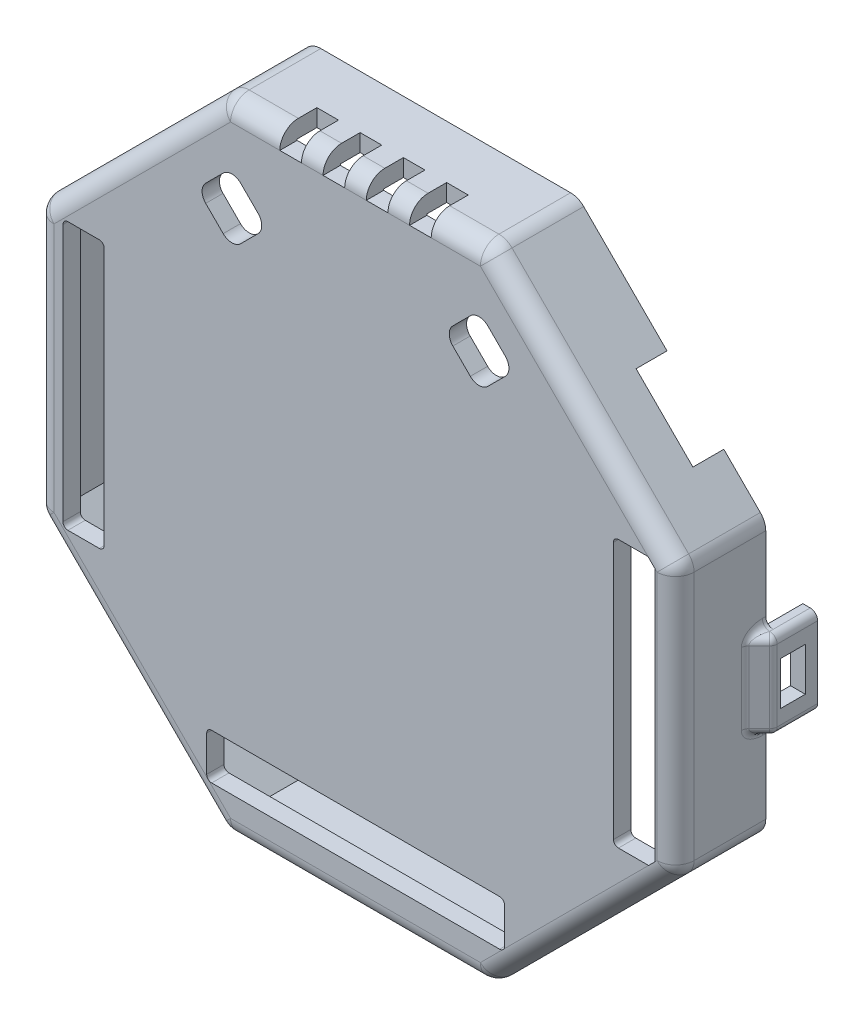
SolidWorks part; units mm, degrees
ref_plane "Front Plane" through (0, 0, 0) normal (0, 0, 1) x (1, 0, 0)
ref_plane "Top Plane" through (0, 0, 0) normal (0, 1, 0) x (1, 0, 0)
ref_plane "Right Plane" through (0, 0, 0) normal (1, 0, 0) x (0, 0, -1)
sketch "Sketch1" plane through (0, 0, 0) normal (0, 0, 1) x (1, 0, 0)
  line L0 (25.9, -10.1068) -> (25.9, 10.1068) construction
  line L1 (25.4607, 11.1675) -> (22.5059, 14.1222) construction
  line L2 (22.5059, 14.1222) -> (21.5159, 13.1323) construction
  line L3 (21.5159, 13.1323) -> (24.5, 10.1482) construction
  line L4 (24.5, 10.1482) -> (24.5, -10.1482) construction
  line L5 (24.5, -10.1482) -> (21.6927, -12.9555) construction
  line L6 (21.6927, -12.9555) -> (22.6827, -13.9455) construction
  line L7 (22.6827, -13.9455) -> (25.4607, -11.1675) construction
  line L8 (-16.1773, -20.4508) -> (-11.1675, -25.4607) construction
  line L9 (-10.1068, -25.9) -> (10.1068, -25.9) construction
  line L10 (11.1675, -25.4607) -> (15.6116, -21.0165) construction
  line L11 (15.6116, -21.0165) -> (14.6216, -20.0266) construction
  line L12 (14.6216, -20.0266) -> (10.1482, -24.5) construction
  line L13 (10.1482, -24.5) -> (-10.1482, -24.5) construction
  line L14 (-10.1482, -24.5) -> (-15.1873, -19.4609) construction
  line L15 (-15.1873, -19.4609) -> (-16.1773, -20.4508) construction
  line L16 (-22.117, 14.5112) -> (-25.4607, 11.1675) construction
  line L17 (-25.9, 10.1068) -> (-25.9, -10.1068) construction
  line L18 (-25.4607, -11.1675) -> (-22.1877, -14.4404) construction
  line L19 (-22.1877, -14.4404) -> (-21.1977, -13.4505) construction
  line L20 (-21.1977, -13.4505) -> (-24.5, -10.1482) construction
  line L21 (-24.5, -10.1482) -> (-24.5, 10.1482) construction
  line L22 (-24.5, 10.1482) -> (-21.127, 13.5212) construction
  line L23 (-21.127, 13.5212) -> (-22.117, 14.5112) construction
  line L24 (10.1068, 25.9) -> (-10.1068, 25.9) construction
  line L25 (-11.1675, 25.4607) -> (-17.5208, 19.1073) construction
  line L26 (-17.5208, 19.1073) -> (-16.5308, 18.1174) construction
  line L27 (-16.5308, 18.1174) -> (-10.1482, 24.5) construction
  line L28 (-10.1482, 24.5) -> (10.1482, 24.5) construction
  line L29 (10.1482, 24.5) -> (16.9197, 17.7285) construction
  line L30 (16.9197, 17.7285) -> (17.9097, 18.7184) construction
  line L31 (17.9097, 18.7184) -> (11.1675, 25.4607) construction
  line L32 (25.9, -10.1068) -> (25.9, 10.1068)
  line L33 (25.4607, 11.1675) -> (22.5059, 14.1222)
  line L34 (22.5059, 14.1222) -> (21.5159, 13.1323)
  line L35 (21.5159, 13.1323) -> (24.5, 10.1482)
  line L36 (24.5, 10.1482) -> (24.5, -10.1482)
  line L37 (24.5, -10.1482) -> (21.6927, -12.9555)
  line L38 (21.6927, -12.9555) -> (22.6827, -13.9455)
  line L39 (22.6827, -13.9455) -> (25.4607, -11.1675)
  line L40 (-16.1773, -20.4508) -> (-11.1675, -25.4607)
  line L41 (-10.1068, -25.9) -> (10.1068, -25.9)
  line L42 (11.1675, -25.4607) -> (15.6116, -21.0165)
  line L43 (15.6116, -21.0165) -> (14.6216, -20.0266)
  line L44 (14.6216, -20.0266) -> (10.1482, -24.5)
  line L45 (10.1482, -24.5) -> (-10.1482, -24.5)
  line L46 (-10.1482, -24.5) -> (-15.1873, -19.4609)
  line L47 (-15.1873, -19.4609) -> (-16.1773, -20.4508)
  line L48 (-22.117, 14.5112) -> (-25.4607, 11.1675)
  line L49 (-25.9, 10.1068) -> (-25.9, -10.1068)
  line L50 (-25.4607, -11.1675) -> (-22.1877, -14.4404)
  line L51 (-22.1877, -14.4404) -> (-21.1977, -13.4505)
  line L52 (-21.1977, -13.4505) -> (-24.5, -10.1482)
  line L53 (-24.5, -10.1482) -> (-24.5, 10.1482)
  line L54 (-24.5, 10.1482) -> (-21.127, 13.5212)
  line L55 (-21.127, 13.5212) -> (-22.117, 14.5112)
  line L56 (10.1068, 25.9) -> (-10.1068, 25.9)
  line L57 (-11.1675, 25.4607) -> (-17.5208, 19.1073)
  line L58 (-17.5208, 19.1073) -> (-16.5308, 18.1174)
  line L59 (-16.5308, 18.1174) -> (-10.1482, 24.5)
  line L60 (-10.1482, 24.5) -> (10.1482, 24.5)
  line L61 (10.1482, 24.5) -> (16.9197, 17.7285)
  line L62 (16.9197, 17.7285) -> (17.9097, 18.7184)
  line L63 (17.9097, 18.7184) -> (11.1675, 25.4607)
  line L66 (-17.5208, 19.1073) -> (-16.5308, 18.1174)
  line L67 (-21.127, 13.5212) -> (-22.117, 14.5112)
  arc A0 (25.9, 10.1068) -> (25.4607, 11.1675) centre (24.4, 10.1068) ccw construction
  arc A1 (25.4607, -11.1675) -> (25.9, -10.1068) centre (24.4, -10.1068) ccw construction
  arc A2 (-11.1675, -25.4607) -> (-10.1068, -25.9) centre (-10.1068, -24.4) ccw construction
  arc A3 (10.1068, -25.9) -> (11.1675, -25.4607) centre (10.1068, -24.4) ccw construction
  arc A4 (-25.4607, 11.1675) -> (-25.9, 10.1068) centre (-24.4, 10.1068) ccw construction
  arc A5 (-25.9, -10.1068) -> (-25.4607, -11.1675) centre (-24.4, -10.1068) ccw construction
  arc A6 (-10.1068, 25.9) -> (-11.1675, 25.4607) centre (-10.1068, 24.4) ccw construction
  arc A7 (11.1675, 25.4607) -> (10.1068, 25.9) centre (10.1068, 24.4) ccw construction
  arc A8 (25.9, 10.1068) -> (25.4607, 11.1675) centre (24.4, 10.1068) ccw
  arc A9 (25.4607, -11.1675) -> (25.9, -10.1068) centre (24.4, -10.1068) ccw
  arc A10 (-11.1675, -25.4607) -> (-10.1068, -25.9) centre (-10.1068, -24.4) ccw
  arc A11 (10.1068, -25.9) -> (11.1675, -25.4607) centre (10.1068, -24.4) ccw
  arc A12 (-25.4607, 11.1675) -> (-25.9, 10.1068) centre (-24.4, 10.1068) ccw
  arc A13 (-25.9, -10.1068) -> (-25.4607, -11.1675) centre (-24.4, -10.1068) ccw
  arc A14 (-10.1068, 25.9) -> (-11.1675, 25.4607) centre (-10.1068, 24.4) ccw
  arc A15 (11.1675, 25.4607) -> (10.1068, 25.9) centre (10.1068, 24.4) ccw
extrude "Boss-Extrude1" add sketch "Sketch1" along normal blind 5 contours L63 A15 L56 A14 L57 L58 L59 L60 L61 L62 | L49 A13 L50 L51 L52 L53 L54 L55 L48 A12 | L41 A11 L42 L43 L44 L45 L46 L47 L40 A10 | L39 A9 L32 A8 L33 L34 L35 L36 L37 L38 region at (24.747, 0.1144, 0) region at (-15.453, -20.1852, 0) region at (-24.631, 0.0454, 0) region at (10.5417, 25.4499, 0)
sketch "Sketch2" plane through (0, 0, 5) normal (0, 0, 1) x (1, 0, 0)
  line L0 (22.6827, -13.9455) -> (25.4607, -11.1675) construction
  line L1 (25.9, -10.1068) -> (25.9, 10.1068) construction
  line L2 (25.4607, 11.1675) -> (22.5059, 14.1222) construction
  line L3 (22.5059, 14.1222) -> (21.5159, 13.1323) construction
  line L4 (21.5159, 13.1323) -> (24.5, 10.1482) construction
  line L5 (24.5, 10.1482) -> (24.5, -10.1482) construction
  line L6 (24.5, -10.1482) -> (21.6927, -12.9555) construction
  line L7 (21.6927, -12.9555) -> (22.6827, -13.9455) construction
  line L8 (-10.1068, -25.9) -> (10.1068, -25.9) construction
  line L9 (11.1675, -25.4607) -> (15.6116, -21.0165) construction
  line L10 (15.6116, -21.0165) -> (14.6216, -20.0266) construction
  line L11 (14.6216, -20.0266) -> (10.1482, -24.5) construction
  line L12 (10.1482, -24.5) -> (-10.1482, -24.5) construction
  line L13 (-10.1482, -24.5) -> (-15.1873, -19.4609) construction
  line L14 (-15.1873, -19.4609) -> (-16.1773, -20.4508) construction
  line L15 (-16.1773, -20.4508) -> (-11.1675, -25.4607) construction
  line L16 (-25.9, 10.1068) -> (-25.9, -10.1068) construction
  line L17 (-25.4607, -11.1675) -> (-22.1877, -14.4404) construction
  line L18 (-22.1877, -14.4404) -> (-21.1977, -13.4505) construction
  line L19 (-21.1977, -13.4505) -> (-24.5, -10.1482) construction
  line L20 (-24.5, -10.1482) -> (-24.5, 10.1482) construction
  line L21 (-24.5, 10.1482) -> (-21.127, 13.5212) construction
  line L22 (-21.127, 13.5212) -> (-22.117, 14.5112) construction
  line L23 (-22.117, 14.5112) -> (-25.4607, 11.1675) construction
  line L24 (17.9097, 18.7184) -> (11.1675, 25.4607) construction
  line L25 (10.1068, 25.9) -> (-10.1068, 25.9) construction
  line L26 (-11.1675, 25.4607) -> (-17.5208, 19.1073) construction
  line L27 (-17.5208, 19.1073) -> (-16.5308, 18.1174) construction
  line L28 (-16.5308, 18.1174) -> (-10.1482, 24.5) construction
  line L29 (-10.1482, 24.5) -> (10.1482, 24.5) construction
  line L30 (10.1482, 24.5) -> (16.9197, 17.7285) construction
  line L31 (16.9197, 17.7285) -> (17.9097, 18.7184) construction
  line L32 (22.6827, -13.9455) -> (25.4607, -11.1675)
  line L33 (25.9, -10.1068) -> (25.9, 10.1068)
  line L34 (25.4607, 11.1675) -> (22.5059, 14.1222)
  line L35 (22.5059, 14.1222) -> (21.5159, 13.1323)
  line L36 (21.5159, 13.1323) -> (24.5, 10.1482)
  line L37 (24.5, 10.1482) -> (24.5, -10.1482)
  line L38 (24.5, -10.1482) -> (21.6927, -12.9555)
  line L39 (21.6927, -12.9555) -> (22.6827, -13.9455)
  line L40 (-10.1068, -25.9) -> (10.1068, -25.9)
  line L41 (11.1675, -25.4607) -> (15.6116, -21.0165)
  line L42 (15.6116, -21.0165) -> (14.6216, -20.0266)
  line L43 (14.6216, -20.0266) -> (10.1482, -24.5)
  line L44 (10.1482, -24.5) -> (-10.1482, -24.5)
  line L45 (-10.1482, -24.5) -> (-15.1873, -19.4609)
  line L46 (-15.1873, -19.4609) -> (-16.1773, -20.4508)
  line L47 (-16.1773, -20.4508) -> (-11.1675, -25.4607)
  line L48 (-25.9, 10.1068) -> (-25.9, -10.1068)
  line L49 (-25.4607, -11.1675) -> (-22.1877, -14.4404)
  line L50 (-22.1877, -14.4404) -> (-21.1977, -13.4505)
  line L51 (-21.1977, -13.4505) -> (-24.5, -10.1482)
  line L52 (-24.5, -10.1482) -> (-24.5, 10.1482)
  line L53 (-24.5, 10.1482) -> (-21.127, 13.5212)
  line L54 (-21.127, 13.5212) -> (-22.117, 14.5112)
  line L55 (-22.117, 14.5112) -> (-25.4607, 11.1675)
  line L56 (17.9097, 18.7184) -> (11.1675, 25.4607)
  line L57 (10.1068, 25.9) -> (-10.1068, 25.9)
  line L58 (-11.1675, 25.4607) -> (-17.5208, 19.1073)
  line L59 (-17.5208, 19.1073) -> (-16.5308, 18.1174)
  line L60 (-16.5308, 18.1174) -> (-10.1482, 24.5)
  line L61 (-10.1482, 24.5) -> (10.1482, 24.5)
  line L62 (10.1482, 24.5) -> (16.9197, 17.7285)
  line L63 (16.9197, 17.7285) -> (17.9097, 18.7184)
  line L64 (-22.117, 14.5112) -> (-17.5208, 19.1073)
  line L65 (-16.5308, 18.1174) -> (-21.127, 13.5212)
  line L66 (-21.1977, -13.4505) -> (-15.1873, -19.4609)
  line L67 (-16.1773, -20.4508) -> (-22.1877, -14.4404)
  line L68 (14.6216, -20.0266) -> (21.6927, -12.9555)
  line L69 (22.6827, -13.9455) -> (15.6116, -21.0165)
  line L70 (22.5059, 14.1222) -> (17.9097, 18.7184)
  line L71 (21.5159, 13.1323) -> (16.9197, 17.7285)
  arc A0 (25.4607, -11.1675) -> (25.9, -10.1068) centre (24.4, -10.1068) ccw construction
  arc A1 (25.9, 10.1068) -> (25.4607, 11.1675) centre (24.4, 10.1068) ccw construction
  arc A2 (10.1068, -25.9) -> (11.1675, -25.4607) centre (10.1068, -24.4) ccw construction
  arc A3 (-11.1675, -25.4607) -> (-10.1068, -25.9) centre (-10.1068, -24.4) ccw construction
  arc A4 (-25.9, -10.1068) -> (-25.4607, -11.1675) centre (-24.4, -10.1068) ccw construction
  arc A5 (-25.4607, 11.1675) -> (-25.9, 10.1068) centre (-24.4, 10.1068) ccw construction
  arc A6 (11.1675, 25.4607) -> (10.1068, 25.9) centre (10.1068, 24.4) ccw construction
  arc A7 (-10.1068, 25.9) -> (-11.1675, 25.4607) centre (-10.1068, 24.4) ccw construction
  arc A8 (25.4607, -11.1675) -> (25.9, -10.1068) centre (24.4, -10.1068) ccw
  arc A9 (25.9, 10.1068) -> (25.4607, 11.1675) centre (24.4, 10.1068) ccw
  arc A10 (10.1068, -25.9) -> (11.1675, -25.4607) centre (10.1068, -24.4) ccw
  arc A11 (-11.1675, -25.4607) -> (-10.1068, -25.9) centre (-10.1068, -24.4) ccw
  arc A12 (-25.9, -10.1068) -> (-25.4607, -11.1675) centre (-24.4, -10.1068) ccw
  arc A13 (-25.4607, 11.1675) -> (-25.9, 10.1068) centre (-24.4, 10.1068) ccw
  arc A14 (11.1675, 25.4607) -> (10.1068, 25.9) centre (10.1068, 24.4) ccw
  arc A15 (-10.1068, 25.9) -> (-11.1675, 25.4607) centre (-10.1068, 24.4) ccw
  line M21 (17.9097, 18.7184) -> (11.1675, 25.4607)
  arc M22 (11.1675, 25.4607) -> (10.1068, 25.9) centre (10.1068, 24.4) ccw
  line M23 (10.1068, 25.9) -> (-10.1068, 25.9)
  arc M24 (-10.1068, 25.9) -> (-11.1675, 25.4607) centre (-10.1068, 24.4) ccw
  line M25 (-11.1675, 25.4607) -> (-17.5208, 19.1073)
  line M26 (-17.5208, 19.1073) -> (-16.5308, 18.1174)
  line M27 (-16.5308, 18.1174) -> (-10.1482, 24.5)
  line M28 (-10.1482, 24.5) -> (10.1482, 24.5)
  line M29 (10.1482, 24.5) -> (16.9197, 17.7285)
  line M30 (16.9197, 17.7285) -> (17.9097, 18.7184)
extrude "Boss-Extrude2" add sketch "Sketch2" along normal blind 1.4 contours L36 L71 L65 L53 L52 L51 L66 L45 L44 L43 L68 L38 L37 M29 M28 M27 | L33 A9 L34 L35 L36 L37 L38 L39 L32 A8 | L69 L39 L68 L42 | L47 A11 L40 A10 L41 L42 L43 L44 L45 L46 | L67 L46 L66 L50 | L55 A13 L48 A12 L49 L50 L51 L52 L53 L54 | L65 L64 L54 M26 | M30 M21 M22 M23 M24 M25 M26 M27 M28 M29 | L71 L35 L70 M30 region at (24.747, 0.1144, 5) region at (18.6522, -16.986, 5) region at (0, 0, 5) region at (13.1602, -23.0093, 5) region at (19.7128, 15.9254, 5) region at (13.7911, 21.3714, 5) region at (-18.6875, -16.9507, 5) region at (-24.631, 0.0454, 5) region at (-19.3239, 16.3143, 5)
sketch "Sketch3" plane through (0, 0, 5) normal (0, 0, -1) x (-1, 0, 0)
  line L0 (-21.5159, 13.1323) -> (-16.9197, 17.7285)
  line L1 (-16.9197, 17.7285) -> (-17.9097, 18.7184)
  line L2 (-17.9097, 18.7184) -> (-22.5059, 14.1222)
  line L3 (-22.5059, 14.1222) -> (-21.5159, 13.1323)
  line L4 (21.127, 13.5212) -> (16.5308, 18.1174)
  line L5 (16.5308, 18.1174) -> (17.5208, 19.1073)
  line L6 (17.5208, 19.1073) -> (22.117, 14.5112)
  line L7 (22.117, 14.5112) -> (21.127, 13.5212)
extrude "Boss-Extrude3" add sketch "Sketch3" along normal blind 3.4 contours L7 L4 L5 L6 | L3 L0 L1 L2
sketch "Sketch4" plane through (0, 0, 5) normal (0, 0, -1) x (-1, 0, 0)
  line L0 (-15.6116, -21.0165) -> (-14.6216, -20.0266)
  line L1 (-14.6216, -20.0266) -> (-21.6927, -12.9555)
  line L2 (-21.6927, -12.9555) -> (-22.6827, -13.9455)
  line L3 (-22.6827, -13.9455) -> (-15.6116, -21.0165)
extrude "Boss-Extrude4" add sketch "Sketch4" along normal blind 3.4
sketch "Sketch5" plane through (0, 0, 5) normal (0, 0, -1) x (-1, 0, 0)
  line L0 (16.1773, -20.4508) -> (22.1877, -14.4404)
  line L1 (22.1877, -14.4404) -> (21.1977, -13.4505)
  line L2 (21.1977, -13.4505) -> (15.1873, -19.4609)
  line L3 (15.1873, -19.4609) -> (16.1773, -20.4508)
extrude "Boss-Extrude5" add sketch "Sketch5" along normal blind 1
fillet "Fillet1" radius 1.5 18 edges at (10.6808, -25.7858, 6.4) (0, -25.9, 6.4) (-10.6808, -25.7858, 6.4) (-18.3141, -18.3141, 6.4) (-25.7858, -10.6808, 6.4) (-25.9, 0, 6.4) (-25.7858, 10.6808, 6.4) (-18.3141, 18.3141, 6.4) (-10.6808, 25.7858, 6.4) (0, 25.9, 6.4) (10.6808, 25.7858, 6.4) (18.3141, 18.3141, 6.4) (25.7858, 10.6808, 6.4) (25.9, 0, 6.4) (25.7858, -10.6808, 6.4) (18.3141, -18.3141, 6.4) (15.1166, -20.5216, 1.6) (22.1877, -13.4505, 1.6)
sketch "Sketch6" plane through (0, 0, 6.4) normal (0, 0, 1) x (1, 0, 0)
  line L0 (-23.2729, -10.394) -> (-20.7329, -10.394) construction
  line L1 (-23.2729, 10.434) -> (-23.2729, -10.394) construction
  line L2 (-20.7329, -10.394) -> (-20.7329, 10.434) construction
  line L3 (-20.7329, 10.434) -> (-23.2729, 10.434) construction
  line L4 (21.2779, -10.389) -> (23.8179, -10.389) construction
  line L5 (23.8179, -10.389) -> (23.8179, 10.439) construction
  line L6 (21.2779, 10.439) -> (21.2779, -10.389) construction
  line L7 (23.8179, 10.439) -> (21.2779, 10.439) construction
  line L8 (-23.2729, -10.394) -> (-20.7329, -10.394)
  line L9 (-23.2729, 10.434) -> (-23.2729, -10.394)
  line L10 (-20.7329, -10.394) -> (-20.7329, 10.434)
  line L11 (-20.7329, 10.434) -> (-23.2729, 10.434)
  line L12 (21.2779, -10.389) -> (23.8179, -10.389)
  line L13 (23.8179, -10.389) -> (23.8179, 10.439)
  line L14 (21.2779, 10.439) -> (21.2779, -10.389)
  line L15 (23.8179, 10.439) -> (21.2779, 10.439)
  line L16 (-20.3329, -10.394) -> (-20.3329, 10.434)
  line L17 (-20.7329, 10.834) -> (-23.2729, 10.834)
  line L18 (-23.6729, 10.434) -> (-23.6729, -10.394)
  line L19 (-23.2729, -10.794) -> (-20.7329, -10.794)
  line L20 (21.2779, -10.789) -> (23.8179, -10.789)
  line L21 (24.2179, -10.389) -> (24.2179, 10.439)
  line L22 (23.8179, 10.839) -> (21.2779, 10.839)
  line L23 (20.8779, 10.439) -> (20.8779, -10.389)
  line L24 (24.2179, 10.839) -> (20.8779, 10.839) construction
  line L25 (20.8779, 10.839) -> (20.8779, -10.789) construction
  line L26 (24.2179, -10.789) -> (24.2179, 10.839) construction
  line L27 (20.8779, -10.789) -> (24.2179, -10.789) construction
  line L28 (-20.3329, -10.794) -> (-20.3329, 10.834) construction
  line L29 (-23.6729, -10.794) -> (-20.3329, -10.794) construction
  line L30 (-23.6729, 10.834) -> (-23.6729, -10.794) construction
  line L31 (-20.3329, 10.834) -> (-23.6729, 10.834) construction
  arc A0 (21.2779, 10.839) -> (20.8779, 10.439) centre (21.2779, 10.439) ccw
  arc A1 (24.2179, 10.439) -> (23.8179, 10.839) centre (23.8179, 10.439) ccw
  arc A2 (23.8179, -10.789) -> (24.2179, -10.389) centre (23.8179, -10.389) ccw
  arc A3 (21.2779, -10.789) -> (20.8779, -10.389) centre (21.2779, -10.389) cw
  arc A4 (-20.3329, -10.394) -> (-20.7329, -10.794) centre (-20.7329, -10.394) cw
  arc A5 (-23.6729, -10.394) -> (-23.2729, -10.794) centre (-23.2729, -10.394) ccw
  arc A6 (-20.3329, 10.434) -> (-20.7329, 10.834) centre (-20.7329, 10.434) ccw
  arc A7 (-23.2729, 10.834) -> (-23.6729, 10.434) centre (-23.2729, 10.434) ccw
  line M15 (10.1068, -24.4) -> (24.4, -10.1068)
  line M17 (24.4, 10.1068) -> (10.1068, 24.4)
  dimension "D2" = 0.4
  dimension "D1" = 0.4
extrude "Cut-Extrude1" cut sketch "Sketch6" against normal through all contours L10 L11 L9 L8 | L17 A7 L18 A5 L19 A4 L16 A6 L11 L10 L8 L9 | L13 L15 L14 L12 | A3 L20 L21 L22 A0 L23 L15 L13 L12 L14 M15 M17 region at (-22.0029, 0.02, 6.4) region at (22.5479, 0.025, 6.4) region at (-20.6048, -10.5221, 6.4) region at (21.1499, -10.5171, 6.4)
sketch "Sketch7" plane through (0, 0, 6.4) normal (0, 0, 1) x (1, 0, 0)
  line L0 (9.3915, -22.0846) -> (11.6775, -22.0846) construction
  line L1 (11.6775, -22.0846) -> (11.6775, -19.5954) construction
  line L2 (-11.1825, -22.0846) -> (-8.8965, -22.0846) construction
  line L3 (-11.1825, -19.5954) -> (-11.1825, -22.0846) construction
  line L4 (9.3915, -22.0846) -> (11.6775, -22.0846)
  line L5 (11.6775, -22.0846) -> (11.6775, -19.5954)
  line L6 (-11.1825, -22.0846) -> (-8.8965, -22.0846)
  line L7 (-11.1825, -19.5954) -> (-11.1825, -22.0846)
  line L8 (-11.1825, -19.5954) -> (11.6775, -19.5954)
  line L9 (9.3915, -22.0846) -> (-8.8965, -22.0846)
  line L10 (9.3915, -22.6846) -> (-8.8965, -22.6846)
  line L11 (-11.6409, -22.6846) -> (-8.8965, -22.6846)
  line L12 (-12.0409, -19.3954) -> (-12.0409, -22.2846)
  line L13 (-11.6409, -18.9954) -> (11.6667, -18.9954)
  line L14 (12.0667, -22.2846) -> (12.0667, -19.3954)
  line L15 (9.3915, -22.6846) -> (11.6667, -22.6846)
  arc A0 (11.6667, -18.9954) -> (12.0667, -19.3954) centre (11.6667, -19.3954) cw
  arc A1 (12.0667, -22.2846) -> (11.6667, -22.6846) centre (11.6667, -22.2846) cw
  arc A2 (-11.6409, -22.6846) -> (-12.0409, -22.2846) centre (-11.6409, -22.2846) cw
  arc A3 (-12.0409, -19.3954) -> (-11.6409, -18.9954) centre (-11.6409, -19.3954) cw
  dimension "D2" = 0.4
  dimension "D1" = 0.6
  dimension "D3" = 0.6
extrude "Cut-Extrude2" cut sketch "Sketch7" against normal through all contours L9 L4 L5 L8 L7 L6 | A3 L12 A2 L11 L10 L15 A1 L14 A0 L13 L4 L9 L6 L7 L8 L5 | L9 L6 L7 L8 L5 L4 | L10 L11 A2 L12 A3 L13 A0 L14 A1 L15 region at (0.2475, -20.84, 6.4) region at (0.2475, -22.4407, 6.4)
sketch "Sketch10" plane through (0, 0, 6.4) normal (0, 0, 1) x (1, 0, 0)
  line L0 (6.3526, -0.709) -> (-6.1073, -0.709)
  line L1 (-6.1073, -0.709) -> (-6.1073, 11.751)
  line L2 (-6.1073, 11.751) -> (6.3526, 11.751)
  line L3 (6.3526, 11.751) -> (6.3526, -0.709)
  line L4 (10.3637, 9.084) -> (10.3637, 10.3555)
  line L5 (9.9467, 10.7717) -> (8.4679, 10.7717)
  line L6 (8.4679, 10.7717) -> (8.4679, 11.7461)
  line L7 (6.3004, 13.9128) -> (5.3733, 13.9128)
  line L8 (5.3733, 13.9128) -> (5.3733, 15.5588)
  line L9 (4.9563, 15.9758) -> (3.6857, 15.9758)
  line L10 (3.2686, 15.5588) -> (3.2686, 13.9128)
  line L11 (3.2686, 13.9128) -> (1.1746, 13.9128)
  line L12 (1.1746, 13.9128) -> (1.1746, 15.5588)
  line L13 (0.7584, 15.9758) -> (-0.5131, 15.9758)
  line L14 (-0.9293, 15.5588) -> (-0.9293, 13.9128)
  line L15 (-0.9293, 13.9128) -> (-2.9507, 13.9128)
  line L16 (-2.9507, 13.9128) -> (-2.9507, 15.5588)
  line L17 (-3.3678, 15.9758) -> (-4.6384, 15.9758)
  line L18 (-5.0554, 15.5588) -> (-5.0554, 13.9128)
  line L19 (-5.0554, 13.9128) -> (-6.0551, 13.9128)
  line L20 (-8.2226, 11.7461) -> (-8.2226, 10.7717)
  line L21 (-8.2226, 10.7717) -> (-9.6287, 10.7717)
  line L22 (-10.0458, 10.3555) -> (-10.0458, 9.084)
  line L23 (-9.6287, 8.6678) -> (-8.2226, 8.6678)
  line L24 (-8.2226, 8.6678) -> (-8.2226, 6.6463)
  line L25 (-8.2226, 6.6463) -> (-9.6287, 6.6463)
  line L26 (-10.0458, 6.2293) -> (-10.0458, 4.9587)
  line L27 (-9.6287, 4.5417) -> (-8.2226, 4.5417)
  line L28 (-8.2226, 4.5417) -> (-8.2226, 2.4476)
  line L29 (-8.2226, 2.4476) -> (-9.6287, 2.4476)
  line L30 (-10.0458, 2.0314) -> (-10.0458, 0.7599)
  line L31 (-9.6287, 0.3437) -> (-8.2226, 0.3437)
  line L32 (-8.2226, 0.3437) -> (-8.2226, -0.6095)
  line L33 (-6.0551, -2.777) -> (-5.0554, -2.777)
  line L34 (-5.0554, -2.777) -> (-5.0554, -4.4434)
  line L35 (-4.6384, -4.8604) -> (-3.3678, -4.8604)
  line L36 (-2.9507, -4.4434) -> (-2.9507, -2.777)
  line L37 (-2.9507, -2.777) -> (-0.8567, -2.777)
  line L38 (-0.8567, -2.777) -> (-0.8567, -4.4434)
  line L39 (-0.4396, -4.8604) -> (0.831, -4.8604)
  line L40 (1.248, -4.4434) -> (1.248, -2.777)
  line L41 (1.248, -2.777) -> (3.2686, -2.777)
  line L42 (3.2686, -2.777) -> (3.2686, -4.4434)
  line L43 (3.6857, -4.8604) -> (4.9563, -4.8604)
  line L44 (5.3733, -4.4434) -> (5.3733, -2.777)
  line L45 (5.3733, -2.777) -> (6.3004, -2.777)
  line L46 (8.4679, -0.6095) -> (8.4679, 0.3437)
  line L47 (8.4679, 0.3437) -> (9.9467, 0.3437)
  line L48 (10.3637, 0.7599) -> (10.3637, 2.0314)
  line L49 (9.9467, 2.4476) -> (8.4679, 2.4476)
  line L50 (8.4679, 2.4476) -> (8.4679, 4.469)
  line L51 (8.4679, 4.469) -> (9.9467, 4.469)
  line L52 (10.3637, 4.8861) -> (10.3637, 6.1567)
  line L53 (9.9467, 6.5737) -> (8.4679, 6.5737)
  line L54 (8.4679, 6.5737) -> (8.4679, 8.6678)
  line L55 (8.4679, 8.6678) -> (9.9467, 8.6678)
  line L56 (-2.4121, 7.0577) -> (-2.4121, 1.1786)
  line L57 (-2.5949, 0.9966) -> (-4.0639, 0.9966)
  line L58 (-4.2459, 1.1786) -> (-4.2459, 7.0577)
  line L59 (-4.2459, 7.0577) -> (-2.4121, 7.0577)
  line L60 (-14.5424, -8.9455) -> (-13.4977, -8.9455)
  line L61 (-13.4977, -8.9455) -> (-13.4977, -12.8799)
  line L62 (-13.4977, -12.8799) -> (-13.5822, -12.9643)
  line L63 (-13.5822, -12.9643) -> (-13.6459, -12.9681)
  line L64 (-13.6459, -12.9681) -> (-14.455, -12.9681)
  line L65 (-14.455, -12.9681) -> (-14.5385, -12.8827)
  line L66 (-14.5385, -12.8827) -> (-14.5424, -12.8198)
  line L67 (-14.5424, -12.8198) -> (-14.5424, -8.9455)
  line L68 (-13.3848, -7.597) -> (-13.3848, -7.6205)
  line L69 (-13.5529, -8.0427) -> (-13.561, -8.0512)
  line L70 (-14.0085, -8.2442) -> (-14.0319, -8.2442)
  line L71 (-14.4569, -8.0698) -> (-14.4636, -8.0631)
  line L72 (-14.6556, -7.6244) -> (-14.6556, -7.5931)
  line L73 (-14.4729, -7.16) -> (-14.4615, -7.1491)
  line L74 (-14.4615, -7.1491) -> (-14.3878, -7.0868)
  line L75 (-14.0358, -6.9733) -> (-14.0045, -6.9733)
  line L76 (-13.5861, -7.1413) -> (-13.5777, -7.1494)
  line L77 (-10.1353, -10.1363) -> (-10.155, -10.1279)
  line L78 (-10.155, -10.1279) -> (-10.1658, -10.1173)
  line L79 (-11.5056, -10.3384) -> (-11.5158, -10.355)
  line L80 (-11.3171, -11.8101) -> (-11.308, -11.8164)
  line L81 (-9.731, -10.9843) -> (-9.731, -10.9723)
  line L82 (-10.7052, -13.0616) -> (-10.7404, -13.0616)
  line L83 (-11.8353, -12.727) -> (-11.8441, -12.721)
  line L84 (-12.7555, -11.0036) -> (-12.7555, -10.9452)
  line L85 (-12.1524, -9.4873) -> (-12.1438, -9.4789)
  line L86 (-9.2496, -9.5351) -> (-9.2455, -9.5393)
  line L87 (-5.8737, -12.7382) -> (-6.0038, -12.793)
  line L88 (-6.8004, -12.9678) -> (-6.8082, -12.9678)
  line L89 (-7.7454, -12.5779) -> (-7.7604, -12.5614)
  line L90 (-7.7604, -12.5614) -> (-7.8266, -12.4749)
  line L91 (-8.0594, -11.7521) -> (-8.0594, -6.9733)
  line L92 (-8.0594, -6.9733) -> (-7.1072, -6.9733)
  line L93 (-7.1072, -6.9733) -> (-7.0226, -7.0577)
  line L94 (-7.0226, -7.0577) -> (-7.0187, -7.1213)
  line L95 (-7.0187, -7.1213) -> (-7.0187, -8.942)
  line L96 (-7.0187, -8.942) -> (-6.1361, -8.942)
  line L97 (-6.1361, -8.942) -> (-6.0512, -9.0261)
  line L98 (-6.0512, -9.0261) -> (-6.0474, -9.09)
  line L99 (-6.0474, -9.09) -> (-6.0474, -9.8979)
  line L100 (-6.0474, -9.8979) -> (-6.1319, -9.9827)
  line L101 (-6.1319, -9.9827) -> (-6.1954, -9.9865)
  line L102 (-6.1954, -9.9865) -> (-7.0187, -9.9865)
  line L103 (-7.0187, -9.9865) -> (-7.0187, -11.7243)
  line L104 (-6.4276, -11.8375) -> (-6.2631, -11.7573)
  line L105 (-6.2631, -11.7573) -> (-5.8737, -12.7382)
  line L106 (-3.3843, -9.9317) -> (-3.4467, -9.9317)
  line L107 (-3.4544, -12.0171) -> (-3.3686, -12.0171)
  line L108 (-1.377, -9.038) -> (-1.377, -12.876)
  line L109 (-1.377, -12.876) -> (-1.4692, -12.9681)
  line L110 (-1.4692, -12.9681) -> (-2.309, -12.9681)
  line L111 (-2.309, -12.9681) -> (-2.4215, -12.8936)
  line L112 (-2.4215, -12.8936) -> (-2.4215, -12.7611)
  line L113 (-3.3998, -13.0616) -> (-3.4036, -13.0616)
  line L114 (-2.4215, -9.2039) -> (-2.4215, -9.0201)
  line L115 (-2.4215, -9.0201) -> (-2.309, -8.9455)
  line L116 (-2.309, -8.9455) -> (-1.4692, -8.9455)
  line L117 (-1.4692, -8.9455) -> (-1.377, -9.038)
  line L118 (4.3331, -11.5371) -> (4.3331, -11.5529)
  line L119 (-0.7141, -10.1572) -> (-0.7141, -10.134)
  line L120 (1.979, -7.2927) -> (1.9868, -7.2927)
  line L121 (1.9516, -12.2427) -> (2.0335, -12.2427)
  line L122 (3.6746, -11.1905) -> (4.3331, -11.5371)
  line L123 (7.7893, -11.1107) -> (7.7893, -11.0991)
  line L124 (6.671, -13.0439) -> (6.6358, -13.0439)
  line L125 (4.7648, -11.13) -> (4.7648, -11.0716)
  line L126 (11.6934, -9.4189) -> (11.6934, -9.4228)
  line L127 (10.8514, -9.953) -> (10.7892, -9.953)
  line L128 (9.9159, -11.2196) -> (9.9159, -12.9349)
  line L129 (9.9159, -12.9349) -> (9.9082, -12.9465)
  line L130 (9.9082, -12.9465) -> (9.179, -12.9465)
  line L131 (9.179, -12.9465) -> (9.1674, -12.9349)
  line L132 (9.1674, -12.9349) -> (9.1674, -9.2748)
  line L133 (9.1674, -9.2748) -> (9.179, -9.2671)
  line L134 (9.179, -9.2671) -> (9.9082, -9.2671)
  line L135 (9.9082, -9.2671) -> (9.9159, -9.2748)
  line L136 (9.9159, -9.2748) -> (9.9159, -9.5553)
  line L137 (10.7966, -9.1929) -> (10.8943, -9.1929)
  line L138 (12.8553, -10.4754) -> (12.7878, -10.6195)
  line L139 (12.7878, -10.6195) -> (14.8381, -10.6195)
  line L140 (14.8381, -10.6195) -> (14.8381, -10.6157)
  line L141 (15.7554, -11.1029) -> (15.7554, -11.22)
  line L142 (15.7385, -11.329) -> (12.7115, -11.329)
  line L143 (13.8193, -13.0439) -> (13.8021, -13.0439)
  line L144 (11.8745, -11.1107) -> (11.8745, -11.0952)
  line L145 (13.7515, -9.1577) -> (13.8741, -9.1577)
  spline S0 degree 3 poles (9.9467, 8.6678) (10.1768, 8.6678) (10.3637, 8.8539) (10.3637, 9.084) knots 0 0 0 0 1 1 1 1
  spline S1 degree 3 poles (10.3637, 10.3555) (10.3637, 10.5856) (10.1768, 10.7717) (9.9467, 10.7717) knots 2 2 2 2 3 3 3 3
  spline S2 degree 3 poles (8.4679, 11.7461) (8.4679, 12.9424) (7.4976, 13.9128) (6.3004, 13.9128) knots 5 5 5 5 6 6 6 6
  spline S3 degree 3 poles (5.3733, 15.5588) (5.3733, 15.7889) (5.1864, 15.9758) (4.9563, 15.9758) knots 8 8 8 8 9 9 9 9
  spline S4 degree 3 poles (3.6857, 15.9758) (3.4555, 15.9758) (3.2686, 15.7889) (3.2686, 15.5588) knots 10 10 10 10 11 11 11 11
  spline S5 degree 3 poles (1.1746, 15.5588) (1.1746, 15.7889) (0.9885, 15.9758) (0.7584, 15.9758) knots 14 14 14 14 15 15 15 15
  spline S6 degree 3 poles (-0.5131, 15.9758) (-0.7432, 15.9758) (-0.9293, 15.7889) (-0.9293, 15.5588) knots 16 16 16 16 17 17 17 17
  spline S7 degree 3 poles (-2.9507, 15.5588) (-2.9507, 15.7889) (-3.1376, 15.9758) (-3.3678, 15.9758) knots 20 20 20 20 21 21 21 21
  spline S8 degree 3 poles (-4.6384, 15.9758) (-4.8685, 15.9758) (-5.0554, 15.7889) (-5.0554, 15.5588) knots 22 22 22 22 23 23 23 23
  spline S9 degree 3 poles (-6.0551, 13.9128) (-7.2523, 13.9128) (-8.2226, 12.9424) (-8.2226, 11.7461) knots 25 25 25 25 26 26 26 26
  spline S10 degree 3 poles (-9.6287, 10.7717) (-9.8589, 10.7717) (-10.0458, 10.5856) (-10.0458, 10.3555) knots 28 28 28 28 29 29 29 29
  spline S11 degree 3 poles (-10.0458, 9.084) (-10.0458, 8.8539) (-9.8589, 8.6678) (-9.6287, 8.6678) knots 30 30 30 30 31 31 31 31
  spline S12 degree 3 poles (-9.6287, 6.6463) (-9.8589, 6.6463) (-10.0458, 6.4595) (-10.0458, 6.2293) knots 34 34 34 34 35 35 35 35
  spline S13 degree 3 poles (-10.0458, 4.9587) (-10.0458, 4.7286) (-9.8589, 4.5417) (-9.6287, 4.5417) knots 36 36 36 36 37 37 37 37
  spline S14 degree 3 poles (-9.6287, 2.4476) (-9.8589, 2.4476) (-10.0458, 2.2615) (-10.0458, 2.0314) knots 40 40 40 40 41 41 41 41
  spline S15 degree 3 poles (-10.0458, 0.7599) (-10.0458, 0.5298) (-9.8589, 0.3437) (-9.6287, 0.3437) knots 42 42 42 42 43 43 43 43
  spline S16 degree 3 poles (-8.2226, -0.6095) (-8.2226, -1.8067) (-7.2523, -2.777) (-6.0551, -2.777) knots 45 45 45 45 46 46 46 46
  spline S17 degree 3 poles (-5.0554, -4.4434) (-5.0554, -4.6736) (-4.8685, -4.8604) (-4.6384, -4.8604) knots 48 48 48 48 49 49 49 49
  spline S18 degree 3 poles (-3.3678, -4.8604) (-3.1376, -4.8604) (-2.9507, -4.6736) (-2.9507, -4.4434) knots 50 50 50 50 51 51 51 51
  spline S19 degree 3 poles (-0.8567, -4.4434) (-0.8567, -4.6736) (-0.6698, -4.8604) (-0.4396, -4.8604) knots 54 54 54 54 55 55 55 55
  spline S20 degree 3 poles (0.831, -4.8604) (1.0611, -4.8604) (1.248, -4.6736) (1.248, -4.4434) knots 56 56 56 56 57 57 57 57
  spline S21 degree 3 poles (3.2686, -4.4434) (3.2686, -4.6736) (3.4555, -4.8604) (3.6857, -4.8604) knots 60 60 60 60 61 61 61 61
  spline S22 degree 3 poles (4.9563, -4.8604) (5.1864, -4.8604) (5.3733, -4.6736) (5.3733, -4.4434) knots 62 62 62 62 63 63 63 63
  spline S23 degree 3 poles (6.3004, -2.777) (7.4976, -2.777) (8.4679, -1.8067) (8.4679, -0.6095) knots 65 65 65 65 66 66 66 66
  spline S24 degree 3 poles (9.9467, 0.3437) (10.1768, 0.3437) (10.3637, 0.5298) (10.3637, 0.7599) knots 68 68 68 68 69 69 69 69
  spline S25 degree 3 poles (10.3637, 2.0314) (10.3637, 2.2615) (10.1768, 2.4476) (9.9467, 2.4476) knots 70 70 70 70 71 71 71 71
  spline S26 degree 3 poles (9.9467, 4.469) (10.1768, 4.469) (10.3637, 4.6559) (10.3637, 4.8861) knots 74 74 74 74 75 75 75 75
  spline S27 degree 3 poles (10.3637, 6.1567) (10.3637, 6.3868) (10.1768, 6.5737) (9.9467, 6.5737) knots 76 76 76 76 77 77 77 77
  spline S28 degree 3 poles (-2.4121, 1.1786) (-2.4121, 1.0782) (-2.4937, 0.9966) (-2.5949, 0.9966) knots 1 1 1 1 2 2 2 2
  spline S29 degree 3 poles (-4.0639, 0.9966) (-4.1643, 0.9966) (-4.2459, 1.0782) (-4.2459, 1.1786) knots 3 3 3 3 4 4 4 4
  spline S30 degree 3 poles (-4.3813, 9.2195) (-4.3813, 9.8005) (-3.9104, 10.2722) (-2.7483, 10.2722) (-2.2766, 9.8005) (-2.2766, 9.2195) knots 2 2 2 2 3 3 4 4 4 4
  spline S31 degree 3 poles (-2.2766, 9.2195) (-2.2766, 8.6384) (-2.7483, 8.1675) (-3.9104, 8.1675) (-4.3813, 8.6384) (-4.3813, 9.2195) knots 0 0 0 0 1 1 2 2 2 2
  spline S32 degree 3 poles (-13.3848, -7.6205) (-13.3848, -7.7724) (-13.4413, -7.9144) (-13.5529, -8.0427) knots 1 1 1 1 2 2 2 2
  spline S33 degree 3 poles (-13.561, -8.0512) (-13.6923, -8.1791) (-13.8429, -8.2442) (-14.0085, -8.2442) knots 3 3 3 3 4 4 4 4
  spline S34 degree 3 poles (-14.0319, -8.2442) (-14.1883, -8.2442) (-14.3312, -8.1855) (-14.4569, -8.0698) knots 5 5 5 5 6 6 6 6
  spline S35 degree 3 poles (-14.4636, -8.0631) (-14.5315, -7.9918) (-14.5766, -7.9274) (-14.6019, -7.8662) knots 7 7 7 7 8 8 8 8
  spline S36 degree 3 poles (-14.6019, -7.8662) (-14.6369, -7.7868) (-14.6556, -7.7042) (-14.6556, -7.6244) knots 8 8 8 8 9 9 9 9
  spline S37 degree 3 poles (-14.6556, -7.5931) (-14.6556, -7.4366) (-14.594, -7.2911) (-14.4729, -7.16) knots 10 10 10 10 11 11 11 11
  spline S38 degree 3 poles (-14.3878, -7.0868) (-14.2734, -7.0116) (-14.1549, -6.9733) (-14.0358, -6.9733) knots 13 13 13 13 14 14 14 14
  spline S39 degree 3 poles (-14.0045, -6.9733) (-13.8549, -6.9733) (-13.7142, -7.0299) (-13.5861, -7.1413) knots 15 15 15 15 16 16 16 16
  spline S40 degree 3 poles (-13.5777, -7.1494) (-13.4497, -7.2809) (-13.3847, -7.4314) (-13.3848, -7.597) knots 17 17 17 17 18 18 18 18
  spline S41 degree 3 poles (-10.0042, -10.2597) (-10.0997, -10.1584) (-10.1318, -10.138) (-10.1353, -10.1363) knots 0 0 0 0 1 1 1 1
  spline S42 degree 3 poles (-10.1658, -10.1173) (-10.2021, -10.0871) (-10.2362, -10.0635) (-10.2668, -10.047) knots 3 3 3 3 4 4 4 4
  spline S43 degree 3 poles (-10.2668, -10.047) (-10.414, -9.9679) (-10.5681, -9.9278) (-10.7249, -9.9278) knots 4 4 4 4 5 5 5 5
  spline S44 degree 3 poles (-10.7249, -9.9278) (-10.9657, -9.9278) (-11.1816, -10.0164) (-11.3846, -10.1989) knots 5 5 5 5 6 6 6 6
  spline S45 degree 3 poles (-11.3846, -10.1989) (-11.4771, -10.2913) (-11.5006, -10.3293) (-11.5056, -10.3384) knots 6 6 6 6 7 7 7 7
  spline S46 degree 3 poles (-11.5158, -10.355) (-11.6497, -10.5416) (-11.7149, -10.7462) (-11.7149, -10.98) knots 8 8 8 8 9 9 9 9
  spline S47 degree 3 poles (-11.7149, -10.98) (-11.7149, -11.2321) (-11.6346, -11.455) (-11.4695, -11.6621) knots 9 9 9 9 10 10 10 10
  spline S48 degree 3 poles (-11.4695, -11.6621) (-11.3808, -11.7619) (-11.3356, -11.7981) (-11.3171, -11.8101) knots 10 10 10 10 11 11 11 11
  spline S49 degree 3 poles (-11.308, -11.8164) (-11.1269, -11.9539) (-10.9362, -12.0207) (-10.7249, -12.0207) knots 12 12 12 12 13 13 13 13
  spline S50 degree 3 poles (-10.7249, -12.0207) (-10.4655, -12.0207) (-10.2408, -11.9247) (-10.0385, -11.7268) knots 13 13 13 13 14 14 14 14
  spline S51 degree 3 poles (-10.0385, -11.7268) (-9.9611, -11.6448) (-9.9047, -11.5721) (-9.8745, -11.5141) knots 14 14 14 14 15 15 15 15
  spline S52 degree 3 poles (-9.8745, -11.5141) (-9.7787, -11.3407) (-9.731, -11.1636) (-9.731, -10.9843) knots 15 15 15 15 16 16 16 16
  spline S53 degree 3 poles (-9.731, -10.9723) (-9.731, -10.7069) (-9.8203, -10.4738) (-10.0042, -10.2597) knots 17 17 17 17 18 18 18 18
  spline S54 degree 3 poles (-8.6901, -10.98) (-8.6901, -11.3295) (-8.7757, -11.6695) (-8.9444, -11.9904) knots 0 0 0 0 1 1 1 1
  spline S55 degree 3 poles (-8.9444, -11.9904) (-9.0042, -12.0987) (-9.0835, -12.2144) (-9.1816, -12.3371) knots 1 1 1 1 2 2 2 2
  spline S56 degree 3 poles (-9.1816, -12.3371) (-9.2946, -12.4675) (-9.3821, -12.5547) (-9.4533, -12.6078) knots 2 2 2 2 3 3 3 3
  spline S57 degree 3 poles (-9.4533, -12.6078) (-9.5231, -12.6651) (-9.5948, -12.7171) (-9.6621, -12.7593) knots 3 3 3 3 4 4 4 4
  spline S58 degree 3 poles (-9.6621, -12.7593) (-9.9945, -12.9604) (-10.3449, -13.0616) (-10.7052, -13.0616) knots 4 4 4 4 5 5 5 5
  spline S59 degree 3 poles (-10.7404, -13.0616) (-11.1202, -13.0616) (-11.4887, -12.9491) (-11.8353, -12.727) knots 6 6 6 6 7 7 7 7
  spline S60 degree 3 poles (-11.8441, -12.721) (-11.909, -12.6725) (-11.967, -12.6264) (-12.0183, -12.5832) knots 8 8 8 8 9 9 9 9
  spline S61 degree 3 poles (-12.0183, -12.5832) (-12.1269, -12.4914) (-12.2048, -12.4134) (-12.256, -12.3455) knots 9 9 9 9 10 10 10 10
  spline S62 degree 3 poles (-12.256, -12.3455) (-12.3136, -12.2791) (-12.3678, -12.2066) (-12.417, -12.13) knots 10 10 10 10 11 11 11 11
  spline S63 degree 3 poles (-12.417, -12.13) (-12.4727, -12.0411) (-12.5202, -11.9542) (-12.5588, -11.8712) knots 11 11 11 11 12 12 12 12
  spline S64 degree 3 poles (-12.5588, -11.8712) (-12.6896, -11.5823) (-12.7555, -11.2908) (-12.7555, -11.0036) knots 12 12 12 12 13 13 13 13
  spline S65 degree 3 poles (-12.7555, -10.9452) (-12.7555, -10.633) (-12.6771, -10.3163) (-12.5223, -10.0041) knots 14 14 14 14 15 15 15 15
  spline S66 degree 3 poles (-12.5223, -10.0041) (-12.4775, -9.9169) (-12.4244, -9.829) (-12.3639, -9.7408) knots 15 15 15 15 16 16 16 16
  spline S67 degree 3 poles (-12.3639, -9.7408) (-12.3147, -9.6715) (-12.2459, -9.5889) (-12.1524, -9.4873) knots 16 16 16 16 17 17 17 17
  spline S68 degree 3 poles (-12.1438, -9.4789) (-12.0067, -9.3527) (-11.9132, -9.2757) (-11.8492, -9.2359) knots 18 18 18 18 19 19 19 19
  spline S69 degree 3 poles (-11.8492, -9.2359) (-11.5122, -9.0057) (-11.1322, -8.8872) (-10.7249, -8.8872) knots 19 19 19 19 20 20 20 20
  spline S70 degree 3 poles (-10.7249, -8.8872) (-10.2705, -8.8872) (-9.8499, -9.0352) (-9.4748, -9.327) knots 20 20 20 20 21 21 21 21
  spline S71 degree 3 poles (-9.4748, -9.327) (-9.4213, -9.3664) (-9.3466, -9.4353) (-9.2496, -9.5351) knots 21 21 21 21 22 22 22 22
  spline S72 degree 3 poles (-9.2455, -9.5393) (-9.0545, -9.7524) (-8.9165, -9.9756) (-8.8351, -10.2027) knots 23 23 23 23 24 24 24 24
  spline S73 degree 3 poles (-8.8351, -10.2027) (-8.7395, -10.4485) (-8.6904, -10.7114) (-8.6901, -10.98) knots 24 24 24 24 25 25 25 25
  spline S74 degree 3 poles (-6.0038, -12.793) (-6.0695, -12.8208) (-6.1739, -12.8556) (-6.323, -12.8996) knots 1 1 1 1 2 2 2 2
  spline S75 degree 3 poles (-6.323, -12.8996) (-6.503, -12.9453) (-6.6619, -12.9678) (-6.8004, -12.9678) knots 2 2 2 2 3 3 3 3
  spline S76 degree 3 poles (-6.8082, -12.9678) (-7.0847, -12.9678) (-7.3457, -12.883) (-7.5844, -12.7157) knots 4 4 4 4 5 5 5 5
  spline S77 degree 3 poles (-7.5844, -12.7157) (-7.6278, -12.6848) (-7.6802, -12.6401) (-7.7454, -12.5779) knots 5 5 5 5 6 6 6 6
  spline S78 degree 3 poles (-7.8266, -12.4749) (-7.875, -12.412) (-7.9135, -12.3483) (-7.9412, -12.2857) knots 8 8 8 8 9 9 9 9
  spline S79 degree 3 poles (-7.9412, -12.2857) (-8.0196, -12.1086) (-8.0594, -11.9289) (-8.0594, -11.7521) knots 9 9 9 9 10 10 10 10
  spline S80 degree 3 poles (-7.0187, -11.7243) (-7.0187, -11.8533) (-6.9708, -11.8772) (-6.9504, -11.8874) knots 23 23 23 23 24 24 24 24
  spline S81 degree 3 poles (-6.9504, -11.8874) (-6.8994, -11.9148) (-6.8526, -11.9271) (-6.8043, -11.9271) knots 24 24 24 24 25 25 25 25
  spline S82 degree 3 poles (-6.8043, -11.9271) (-6.7466, -11.9271) (-6.6347, -11.9117) (-6.4276, -11.8375) knots 25 25 25 25 26 26 26 26
  spline S83 degree 3 poles (-2.8874, -10.0871) (-3.0568, -9.9841) (-3.2242, -9.9317) (-3.3843, -9.9317) knots 0 0 0 0 1 1 1 1
  spline S84 degree 3 poles (-3.4467, -9.9317) (-3.7155, -9.9317) (-3.9549, -10.0554) (-4.1788, -10.3096) knots 2 2 2 2 3 3 3 3
  spline S85 degree 3 poles (-4.1788, -10.3096) (-4.3288, -10.5237) (-4.4015, -10.7406) (-4.4015, -10.9723) knots 3 3 3 3 4 4 4 4
  spline S86 degree 3 poles (-4.4015, -10.9723) (-4.4015, -11.3362) (-4.249, -11.6269) (-3.9352, -11.8621) knots 4 4 4 4 5 5 5 5
  spline S87 degree 3 poles (-3.9352, -11.8621) (-3.7636, -11.9648) (-3.6019, -12.0171) (-3.4544, -12.0171) knots 5 5 5 5 6 6 6 6
  spline S88 degree 3 poles (-3.3686, -12.0171) (-3.1545, -12.0171) (-2.9496, -11.9303) (-2.7425, -11.7521) knots 7 7 7 7 8 8 8 8
  spline S89 degree 3 poles (-2.7425, -11.7521) (-2.5267, -11.5295) (-2.4215, -11.2757) (-2.4215, -10.9765) knots 8 8 8 8 9 9 9 9
  spline S90 degree 3 poles (-2.4215, -10.9765) (-2.4215, -10.6042) (-2.5738, -10.3145) (-2.8874, -10.0871) knots 9 9 9 9 10 10 10 10
  spline S91 degree 3 poles (-2.4215, -12.7611) (-2.6965, -12.9607) (-3.0241, -13.0616) (-3.3998, -13.0616) knots 5 5 5 5 6 6 6 6
  spline S92 degree 3 poles (-3.4036, -13.0616) (-4.0139, -13.0616) (-4.5385, -12.8127) (-4.9628, -12.322) knots 7 7 7 7 8 8 8 8
  spline S93 degree 3 poles (-4.9628, -12.322) (-5.282, -11.9215) (-5.4422, -11.4701) (-5.4422, -10.9765) knots 8 8 8 8 9 9 9 9
  spline S94 degree 3 poles (-5.4422, -10.9765) (-5.4422, -10.362) (-5.204, -9.8283) (-4.7341, -9.3864) knots 9 9 9 9 10 10 10 10
  spline S95 degree 3 poles (-4.7341, -9.3864) (-4.3365, -9.0531) (-3.887, -8.8872) (-3.392, -8.8872) knots 10 10 10 10 11 11 11 11
  spline S96 degree 3 poles (-3.392, -8.8872) (-3.0301, -8.8872) (-2.7049, -8.9934) (-2.4215, -9.2039) knots 11 11 11 11 12 12 12 12
  spline S97 degree 3 poles (4.3331, -11.5529) (4.2449, -11.7164) (4.1278, -11.8894) (3.9822, -12.0711) knots 1 1 1 1 2 2 2 2
  spline S98 degree 3 poles (3.9822, -12.0711) (3.4159, -12.6895) (2.7507, -12.9989) (1.9868, -12.9989) knots 2 2 2 2 3 3 3 3
  spline S99 degree 3 poles (1.9868, -12.9989) (1.2281, -12.9989) (0.5656, -12.6948) (-0.0008, -12.0869) knots 3 3 3 3 4 4 4 4
  spline S100 degree 3 poles (-0.0008, -12.0869) (-0.4765, -11.5125) (-0.7141, -10.8695) (-0.7141, -10.1572) knots 4 4 4 4 5 5 5 5
  spline S101 degree 3 poles (-0.7141, -10.134) (-0.7141, -9.4144) (-0.4726, -8.7685) (0.0108, -8.1969) knots 6 6 6 6 7 7 7 7
  spline S102 degree 3 poles (0.0108, -8.1969) (0.5723, -7.594) (1.2281, -7.2927) (1.979, -7.2927) knots 7 7 7 7 8 8 8 8
  spline S103 degree 3 poles (1.9868, -7.2927) (2.7222, -7.2927) (3.3652, -7.5785) (3.9161, -8.1501) knots 9 9 9 9 10 10 10 10
  spline S104 degree 3 poles (3.9161, -8.1501) (4.1109, -8.3737) (4.2487, -8.5657) (4.3292, -8.7271) knots 10 10 10 10 11 11 11 11
  spline S105 degree 3 poles (4.3292, -8.7271) (4.3085, -8.7453) (4.0891, -8.8659) (3.6707, -9.0895) knots 11 11 11 11 12 12 12 12
  spline S106 degree 3 poles (3.6707, -9.0895) (3.6004, -8.9623) (3.4953, -8.8153) (3.355, -8.649) knots 12 12 12 12 13 13 13 13
  spline S107 degree 3 poles (3.355, -8.649) (2.9522, -8.2437) (2.4958, -8.0412) (1.9868, -8.0412) knots 13 13 13 13 14 14 14 14
  spline S108 degree 3 poles (1.9868, -8.0412) (1.4696, -8.0412) (1.0108, -8.2461) (0.6109, -8.6567) knots 14 14 14 14 15 15 15 15
  spline S109 degree 3 poles (0.6109, -8.6567) (0.2263, -9.0909) (0.034, -9.5859) (0.034, -10.1417) knots 15 15 15 15 16 16 16 16
  spline S110 degree 3 poles (0.034, -10.1417) (0.034, -10.7865) (0.2798, -11.336) (0.7707, -11.7906) knots 16 16 16 16 17 17 17 17
  spline S111 degree 3 poles (0.7707, -11.7906) (1.142, -12.0922) (1.5357, -12.2427) (1.9516, -12.2427) knots 17 17 17 17 18 18 18 18
  spline S112 degree 3 poles (2.0335, -12.2427) (2.4909, -12.2427) (2.9184, -12.0542) (3.316, -11.6777) knots 19 19 19 19 20 20 20 20
  spline S113 degree 3 poles (3.316, -11.6777) (3.4848, -11.4907) (3.6043, -11.3283) (3.6746, -11.1905) knots 20 20 20 20 21 21 21 21
  spline S114 degree 3 poles (7.7893, -11.0991) (7.7893, -10.8002) (7.687, -10.5313) (7.4817, -10.2922) knots 0 0 0 0 1 1 1 1
  spline S115 degree 3 poles (7.4817, -10.2922) (7.3931, -10.1983) (7.3337, -10.1453) (7.3024, -10.1323) knots 1 1 1 1 2 2 2 2
  spline S116 degree 3 poles (7.3024, -10.1323) (7.2581, -10.0957) (7.2166, -10.0672) (7.1776, -10.0465) knots 2 2 2 2 3 3 3 3
  spline S117 degree 3 poles (7.1776, -10.0465) (7.0085, -9.9554) (6.8331, -9.9101) (6.6513, -9.9101) knots 3 3 3 3 4 4 4 4
  spline S118 degree 3 poles (6.6513, -9.9101) (6.376, -9.9101) (6.124, -10.0127) (5.8951, -10.218) knots 4 4 4 4 5 5 5 5
  spline S119 degree 3 poles (5.8951, -10.218) (5.8146, -10.2985) (5.764, -10.3583) (5.7432, -10.3973) knots 5 5 5 5 6 6 6 6
  spline S120 degree 3 poles (5.7432, -10.3973) (5.5924, -10.6076) (5.5172, -10.8442) (5.5172, -11.1064) knots 6 6 6 6 7 7 7 7
  spline S121 degree 3 poles (5.5172, -11.1064) (5.5172, -11.3898) (5.6093, -11.6471) (5.7938, -11.8785) knots 7 7 7 7 8 8 8 8
  spline S122 degree 3 poles (5.7938, -11.8785) (5.8743, -11.9692) (5.9366, -12.0289) (5.9809, -12.0574) knots 8 8 8 8 9 9 9 9
  spline S123 degree 3 poles (5.9809, -12.0574) (6.1862, -12.2135) (6.4098, -12.2916) (6.6513, -12.2916) knots 9 9 9 9 10 10 10 10
  spline S124 degree 3 poles (6.6513, -12.2916) (6.9477, -12.2916) (7.2099, -12.1798) (7.4388, -11.9565) knots 10 10 10 10 11 11 11 11
  spline S125 degree 3 poles (7.4388, -11.9565) (7.5295, -11.8602) (7.5931, -11.7769) (7.6297, -11.7069) knots 11 11 11 11 12 12 12 12
  spline S126 degree 3 poles (7.6297, -11.7069) (7.7362, -11.5146) (7.7893, -11.316) (7.7893, -11.1107) knots 12 12 12 12 13 13 13 13
  spline S127 degree 3 poles (8.542, -11.1068) (8.542, -11.4341) (8.4625, -11.7484) (8.304, -12.05) knots 0 0 0 0 1 1 1 1
  spline S128 degree 3 poles (8.304, -12.05) (8.2495, -12.1488) (8.1757, -12.2564) (8.0818, -12.3735) knots 1 1 1 1 2 2 2 2
  spline S129 degree 3 poles (8.0818, -12.3735) (7.9806, -12.4905) (7.8986, -12.5725) (7.8364, -12.6189) knots 2 2 2 2 3 3 3 3
  spline S130 degree 3 poles (7.8364, -12.6189) (7.7661, -12.6762) (7.7, -12.7243) (7.6374, -12.7633) knots 3 3 3 3 4 4 4 4
  spline S131 degree 3 poles (7.6374, -12.7633) (7.3284, -12.9504) (7.006, -13.0439) (6.671, -13.0439) knots 4 4 4 4 5 5 5 5
  spline S132 degree 3 poles (6.6358, -13.0439) (6.2825, -13.0439) (5.9432, -12.9402) (5.6188, -12.7321) knots 6 6 6 6 7 7 7 7
  spline S133 degree 3 poles (5.6188, -12.7321) (5.5562, -12.6853) (5.5003, -12.6414) (5.4511, -12.5995) knots 7 7 7 7 8 8 8 8
  spline S134 degree 3 poles (5.4511, -12.5995) (5.3495, -12.5137) (5.2767, -12.441) (5.2327, -12.3812) knots 8 8 8 8 9 9 9 9
  spline S135 degree 3 poles (5.2327, -12.3812) (5.1782, -12.319) (5.1273, -12.2515) (5.0805, -12.1787) knots 9 9 9 9 10 10 10 10
  spline S136 degree 3 poles (5.0805, -12.1787) (5.0288, -12.0954) (4.9845, -12.0149) (4.9483, -11.9368) knots 10 10 10 10 11 11 11 11
  spline S137 degree 3 poles (4.9483, -11.9368) (4.826, -11.6668) (4.7648, -11.3975) (4.7648, -11.13) knots 11 11 11 11 12 12 12 12
  spline S138 degree 3 poles (4.7648, -11.0716) (4.7648, -10.7809) (4.8376, -10.4884) (4.9831, -10.1948) knots 13 13 13 13 14 14 14 14
  spline S139 degree 3 poles (4.9831, -10.1948) (5.025, -10.114) (5.0742, -10.0324) (5.1315, -9.9491) knots 14 14 14 14 15 15 15 15
  spline S140 degree 3 poles (5.1315, -9.9491) (5.1754, -9.8865) (5.2419, -9.8074) (5.3301, -9.7114) knots 15 15 15 15 16 16 16 16
  spline S141 degree 3 poles (5.3301, -9.7114) (5.4574, -9.5944) (5.5484, -9.5191) (5.6029, -9.485) knots 16 16 16 16 17 17 17 17
  spline S142 degree 3 poles (5.6029, -9.485) (5.9225, -9.2671) (6.272, -9.1577) (6.6513, -9.1577) knots 17 17 17 17 18 18 18 18
  spline S143 degree 3 poles (6.6513, -9.1577) (7.0749, -9.1577) (7.4624, -9.2941) (7.8129, -9.5669) knots 18 18 18 18 19 19 19 19
  spline S144 degree 3 poles (7.8129, -9.5669) (7.8621, -9.6035) (7.9324, -9.6682) (8.0234, -9.7621) knots 19 19 19 19 20 20 20 20
  spline S145 degree 3 poles (8.0234, -9.7621) (8.2027, -9.9621) (8.33, -10.1674) (8.4052, -10.3776) knots 20 20 20 20 21 21 21 21
  spline S146 degree 3 poles (8.4052, -10.3776) (8.4963, -10.6118) (8.5416, -10.8547) (8.542, -11.1068) knots 21 21 21 21 22 22 22 22
  spline S147 degree 3 poles (11.6934, -9.4228) (11.5841, -9.9164) (11.5243, -10.1751) (11.5141, -10.1983) knots 1 1 1 1 2 2 2 2
  spline S148 degree 3 poles (11.5141, -10.1983) (11.2645, -10.0349) (11.0437, -9.953) (10.8514, -9.953) knots 2 2 2 2 3 3 3 3
  spline S149 degree 3 poles (10.7892, -9.953) (10.5396, -9.953) (10.3199, -10.0451) (10.1304, -10.2296) knots 4 4 4 4 5 5 5 5
  spline S150 degree 3 poles (10.1304, -10.2296) (9.9873, -10.4037) (9.9159, -10.7338) (9.9159, -11.2196) knots 5 5 5 5 6 6 6 6
  spline S151 degree 3 poles (9.9159, -9.5553) (10.2017, -9.3138) (10.4953, -9.1929) (10.7966, -9.1929) knots 15 15 15 15 16 16 16 16
  spline S152 degree 3 poles (10.8943, -9.1929) (11.1513, -9.1929) (11.4178, -9.2681) (11.6934, -9.4189) knots 17 17 17 17 18 18 18 18
  spline S153 degree 3 poles (14.8381, -10.6157) (14.7903, -10.4831) (14.6803, -10.3323) (14.5084, -10.1635) knots 0 0 0 0 1 1 1 1
  spline S154 degree 3 poles (14.5084, -10.1635) (14.2939, -9.9944) (14.0601, -9.9101) (13.8066, -9.9101) knots 1 1 1 1 2 2 2 2
  spline S155 degree 3 poles (13.8066, -9.9101) (13.4203, -9.9101) (13.1032, -10.0985) (12.8553, -10.4754) knots 2 2 2 2 3 3 3 3
  spline S156 degree 3 poles (15.7554, -11.22) (15.7554, -11.2928) (15.7497, -11.329) (15.7385, -11.329) knots 1 1 1 1 2 2 2 2
  spline S157 degree 3 poles (12.7115, -11.329) (12.7762, -11.6071) (12.8834, -11.8148) (13.0329, -11.9526) knots 3 3 3 3 4 4 4 4
  spline S158 degree 3 poles (13.0329, -11.9526) (13.261, -12.1787) (13.5205, -12.2916) (13.8109, -12.2916) knots 4 4 4 4 5 5 5 5
  spline S159 degree 3 poles (13.8109, -12.2916) (14.1772, -12.2916) (14.4845, -12.1214) (14.7323, -11.7811) knots 5 5 5 5 6 6 6 6
  spline S160 degree 3 poles (14.7323, -11.7811) (14.7801, -11.6953) (14.8086, -11.651) (14.817, -11.6485) knots 6 6 6 6 7 7 7 7
  spline S161 degree 3 poles (14.817, -11.6485) (15.3015, -11.851) (15.5469, -11.9551) (15.5525, -11.9604) knots 7 7 7 7 8 8 8 8
  spline S162 degree 3 poles (15.5525, -11.9604) (15.5131, -12.0514) (15.4242, -12.1878) (15.2864, -12.3696) knots 8 8 8 8 9 9 9 9
  spline S163 degree 3 poles (15.2864, -12.3696) (14.8719, -12.8192) (14.3829, -13.0439) (13.8193, -13.0439) knots 9 9 9 9 10 10 10 10
  spline S164 degree 3 poles (13.8021, -13.0439) (13.2216, -13.0439) (12.7228, -12.8062) (12.3058, -12.3306) knots 11 11 11 11 12 12 12 12
  spline S165 degree 3 poles (12.3058, -12.3306) (12.0182, -11.959) (11.8745, -11.5526) (11.8745, -11.1107) knots 12 12 12 12 13 13 13 13
  spline S166 degree 3 poles (11.8745, -11.0952) (11.8745, -10.487) (12.1265, -9.9726) (12.6314, -9.5515) knots 14 14 14 14 15 15 15 15
  spline S167 degree 3 poles (12.6314, -9.5515) (13.0033, -9.2892) (13.3767, -9.1577) (13.7515, -9.1577) knots 15 15 15 15 16 16 16 16
  spline S168 degree 3 poles (13.8741, -9.1577) (14.2855, -9.1577) (14.6817, -9.31) (15.0621, -9.6137) knots 17 17 17 17 18 18 18 18
  spline S169 degree 3 poles (15.0621, -9.6137) (15.2481, -9.7828) (15.3764, -9.9283) (15.4467, -10.0503) knots 18 18 18 18 19 19 19 19
  spline S170 degree 3 poles (15.4467, -10.0503) (15.6527, -10.3854) (15.7554, -10.7362) (15.7554, -11.1029) knots 19 19 19 19 20 20 20 20
extrude "Cut-Extrude3" [suppressed] cut sketch "Sketch10" against normal blind 0.2 contours L52 S27 L53 L54 L55 S0 L4 S1 L5 L6 S2 L7 L8 S3 L9 S4 L10 L11 L12 S5 L13 S6 L14 L15 L16 S7 L17 S8 L18 L19 S9 L20 L21 S10 L22 S11 L23 L24 L25 S12 L26 S13 L27 L28 L29 S14 L30 S15 L31 L32 S16 | S29 L57 S28 L56 L59 L58 | S31 S30 | S82 S81 S80 L103 L102 L101 L100 L99 L98 L97 L96 L95 L94 L93 L92 L91 S79 S78 L90 L89 S77 S76 L88 S75 S74 L87 L105 L104 | S73 S72 L86 S71 S70 S69 S68 L85 S67 S66 S65 L84 S64 S63 S62 S61 S60 L83 S59 L82 S58 S57 S56 S55 S54 S53 L81 S52 S51 S50 S49 L80 S48 S47 S46 L79 S45 S44 S43 S42 L78 L77 S41 | L67 L66 L65 L64 L63 L62 L61 L60 | S40 L76 S39 L75 S38 L74 L73 S37 L72 S36 S35 L71 S34 L70 S33 L69 S32 L68 | S96 S95 S94 S93 S92 L113 S91 L112 L111 L110 L109 L108 L117 L116 L115 L114 S90 S89 S88 L107 S87 S86 S85 S84 L106 S83 | S113 S112 L121 S111 S110 S109 S108 S107 S106 S105 S104 S103 L120 S102 S101 L119 S100 S99 S98 S97 L118 L122 | S170 S169 S168 L145 S167 S166 L144 S165 S164 L143 S163 S162 S161 S160 S159 S158 S157 L142 S156 L141 S155 S154 S153 L140 L139 L138 | S152 L137 S151 L136 L135 L134 L133 L132 L131 L130 L129 L128 S150 S149 L127 S148 S147 L126 | S146 S145 S144 S143 S142 S141 S140 S139 S138 L125 S137 S136 S135 S134 S133 S132 L124 S131 S130 S129 S128 S127 S126 S125 S124 S123 S122 S121 S120 S119 S118 S117 S116 S115 S114 L123
sketch "Sketch12" plane through (0, 0, 0) normal (0, 0, -1) x (-1, 0, 0)
  line L0 (-24.5, 10.1482) -> (-24.5, -10.1482) construction
  line L1 (-24.5, -10.1482) -> (-10.1482, -24.5) construction
  line L2 (-10.1482, -24.5) -> (10.1482, -24.5) construction
  line L3 (10.1482, -24.5) -> (24.5, -10.1482) construction
  line L4 (24.5, -10.1482) -> (24.5, 10.1482) construction
  line L5 (24.5, 10.1482) -> (21.127, 13.5212) construction
  line L6 (21.127, 13.5212) -> (16.5308, 18.1174) construction
  line L7 (16.5308, 18.1174) -> (10.1482, 24.5) construction
  line L8 (10.1482, 24.5) -> (-10.1482, 24.5) construction
  line L9 (-10.1482, 24.5) -> (-24.5, 10.1482) construction
  line L10 (-24.5, 10.1482) -> (-24.5, -10.1482)
  line L11 (-24.5, -10.1482) -> (-10.1482, -24.5)
  line L12 (-10.1482, -24.5) -> (10.1482, -24.5)
  line L13 (10.1482, -24.5) -> (24.5, -10.1482)
  line L14 (24.5, -10.1482) -> (24.5, 10.1482)
  line L15 (24.5, 10.1482) -> (21.127, 13.5212)
  line L16 (21.127, 13.5212) -> (16.5308, 18.1174)
  line L17 (16.5308, 18.1174) -> (10.1482, 24.5)
  line L18 (10.1482, 24.5) -> (-10.1482, 24.5)
  line L19 (-10.1482, 24.5) -> (-24.5, 10.1482)
  line L20 (-25.25, 10.4589) -> (-25.25, -10.4589)
  line L21 (-25.25, -10.4589) -> (-10.4589, -25.25)
  line L22 (-10.4589, -25.25) -> (10.4589, -25.25)
  line L23 (10.4589, -25.25) -> (25.25, -10.4589)
  line L24 (25.25, -10.4589) -> (25.25, 10.4589)
  line L25 (25.25, 10.4589) -> (21.6574, 14.0515)
  line L26 (21.6574, 14.0515) -> (17.0612, 18.6477)
  line L27 (17.0612, 18.6477) -> (10.4589, 25.25)
  line L28 (10.4589, 25.25) -> (-10.4589, 25.25)
  line L29 (-10.4589, 25.25) -> (-25.25, 10.4589)
  line L30 (-25.4607, -11.1675) -> (-22.6827, -13.9455) construction
  line L31 (-22.6827, -13.9455) -> (-21.6927, -12.9555) construction
  line L32 (-21.6927, -12.9555) -> (-24.5, -10.1482) construction
  line L33 (-24.5, -10.1482) -> (-24.5, 10.1482) construction
  line L34 (-24.5, 10.1482) -> (-21.5159, 13.1323) construction
  line L35 (-21.5159, 13.1323) -> (-22.5059, 14.1222) construction
  line L36 (-22.5059, 14.1222) -> (-25.4607, 11.1675) construction
  line L37 (-25.9, 10.1068) -> (-25.9, -10.1068) construction
  line L38 (-10.1068, -25.9) -> (10.1068, -25.9) construction
  line L39 (11.1675, -25.4607) -> (16.1773, -20.4508) construction
  line L40 (16.1773, -20.4508) -> (15.1873, -19.4609) construction
  line L41 (15.1873, -19.4609) -> (10.1482, -24.5) construction
  line L42 (10.1482, -24.5) -> (-10.1482, -24.5) construction
  line L43 (-10.1482, -24.5) -> (-14.6216, -20.0266) construction
  line L44 (-14.6216, -20.0266) -> (-15.6116, -21.0165) construction
  line L45 (-15.6116, -21.0165) -> (-11.1675, -25.4607) construction
  line L46 (25.9, -10.1068) -> (25.9, 10.1068) construction
  line L47 (25.4607, 11.1675) -> (22.117, 14.5112) construction
  line L48 (22.117, 14.5112) -> (21.127, 13.5212) construction
  line L49 (21.127, 13.5212) -> (24.5, 10.1482) construction
  line L50 (24.5, 10.1482) -> (24.5, -10.1482) construction
  line L51 (24.5, -10.1482) -> (21.1977, -13.4505) construction
  line L52 (21.1977, -13.4505) -> (22.1877, -14.4404) construction
  line L53 (22.1877, -14.4404) -> (25.4607, -11.1675) construction
  line L54 (-11.1675, 25.4607) -> (-17.9097, 18.7184) construction
  line L55 (-17.9097, 18.7184) -> (-16.9197, 17.7285) construction
  line L56 (-16.9197, 17.7285) -> (-10.1482, 24.5) construction
  line L57 (-10.1482, 24.5) -> (10.1482, 24.5) construction
  line L58 (10.1482, 24.5) -> (16.5308, 18.1174) construction
  line L59 (16.5308, 18.1174) -> (17.5208, 19.1073) construction
  line L60 (17.5208, 19.1073) -> (11.1675, 25.4607) construction
  line L61 (10.1068, 25.9) -> (-10.1068, 25.9) construction
  line L62 (-25.4607, -11.1675) -> (-22.6827, -13.9455)
  line L63 (-22.6827, -13.9455) -> (-21.6927, -12.9555)
  line L64 (-21.6927, -12.9555) -> (-24.5, -10.1482)
  line L65 (-24.5, -10.1482) -> (-24.5, 10.1482)
  line L66 (-24.5, 10.1482) -> (-21.5159, 13.1323)
  line L67 (-21.5159, 13.1323) -> (-22.5059, 14.1222)
  line L68 (-22.5059, 14.1222) -> (-25.4607, 11.1675)
  line L69 (-25.9, 10.1068) -> (-25.9, -10.1068)
  line L70 (-10.1068, -25.9) -> (10.1068, -25.9)
  line L71 (11.1675, -25.4607) -> (16.1773, -20.4508)
  line L72 (16.1773, -20.4508) -> (15.1873, -19.4609)
  line L73 (15.1873, -19.4609) -> (10.1482, -24.5)
  line L74 (10.1482, -24.5) -> (-10.1482, -24.5)
  line L75 (-10.1482, -24.5) -> (-14.6216, -20.0266)
  line L76 (-14.6216, -20.0266) -> (-15.6116, -21.0165)
  line L77 (-15.6116, -21.0165) -> (-11.1675, -25.4607)
  line L78 (25.9, -10.1068) -> (25.9, 10.1068)
  line L79 (25.4607, 11.1675) -> (22.117, 14.5112)
  line L80 (22.117, 14.5112) -> (21.127, 13.5212)
  line L81 (21.127, 13.5212) -> (24.5, 10.1482)
  line L82 (24.5, 10.1482) -> (24.5, -10.1482)
  line L83 (24.5, -10.1482) -> (21.1977, -13.4505)
  line L84 (21.1977, -13.4505) -> (22.1877, -14.4404)
  line L85 (22.1877, -14.4404) -> (25.4607, -11.1675)
  line L86 (-11.1675, 25.4607) -> (-17.9097, 18.7184)
  line L87 (-17.9097, 18.7184) -> (-16.9197, 17.7285)
  line L88 (-16.9197, 17.7285) -> (-10.1482, 24.5)
  line L89 (-10.1482, 24.5) -> (10.1482, 24.5)
  line L90 (10.1482, 24.5) -> (16.5308, 18.1174)
  line L91 (16.5308, 18.1174) -> (17.5208, 19.1073)
  line L92 (17.5208, 19.1073) -> (11.1675, 25.4607)
  line L93 (10.1068, 25.9) -> (-10.1068, 25.9)
  arc A0 (-25.4607, 11.1675) -> (-25.9, 10.1068) centre (-24.4, 10.1068) ccw construction
  arc A1 (-25.9, -10.1068) -> (-25.4607, -11.1675) centre (-24.4, -10.1068) ccw construction
  arc A2 (10.1068, -25.9) -> (11.1675, -25.4607) centre (10.1068, -24.4) ccw construction
  arc A3 (-11.1675, -25.4607) -> (-10.1068, -25.9) centre (-10.1068, -24.4) ccw construction
  arc A4 (25.9, 10.1068) -> (25.4607, 11.1675) centre (24.4, 10.1068) ccw construction
  arc A5 (25.4607, -11.1675) -> (25.9, -10.1068) centre (24.4, -10.1068) ccw construction
  arc A6 (11.1675, 25.4607) -> (10.1068, 25.9) centre (10.1068, 24.4) ccw construction
  arc A7 (-10.1068, 25.9) -> (-11.1675, 25.4607) centre (-10.1068, 24.4) ccw construction
  arc A8 (-25.4607, 11.1675) -> (-25.9, 10.1068) centre (-24.4, 10.1068) ccw
  arc A9 (-25.9, -10.1068) -> (-25.4607, -11.1675) centre (-24.4, -10.1068) ccw
  arc A10 (10.1068, -25.9) -> (11.1675, -25.4607) centre (10.1068, -24.4) ccw
  arc A11 (-11.1675, -25.4607) -> (-10.1068, -25.9) centre (-10.1068, -24.4) ccw
  arc A12 (25.9, 10.1068) -> (25.4607, 11.1675) centre (24.4, 10.1068) ccw
  arc A13 (25.4607, -11.1675) -> (25.9, -10.1068) centre (24.4, -10.1068) ccw
  arc A14 (11.1675, 25.4607) -> (10.1068, 25.9) centre (10.1068, 24.4) ccw
  arc A15 (-10.1068, 25.9) -> (-11.1675, 25.4607) centre (-10.1068, 24.4) ccw
  line M1 (-10.1068, -25.9) -> (10.1068, -25.9)
  arc M2 (10.1068, -25.9) -> (11.1675, -25.4607) centre (10.1068, -24.4) ccw
  line M3 (11.1675, -25.4607) -> (16.1773, -20.4508)
  line M4 (16.1773, -20.4508) -> (15.1873, -19.4609)
  line M8 (-14.6216, -20.0266) -> (-15.6116, -21.0165)
  line M9 (-15.6116, -21.0165) -> (-11.1675, -25.4607)
  arc M10 (-11.1675, -25.4607) -> (-10.1068, -25.9) centre (-10.1068, -24.4) ccw
  dimension "D1" = 0.75
extrude "Boss-Extrude6" add sketch "Sketch12" along normal blind 0.9 contours L69 A9 L62 L63 L21 L20 L29 L67 L68 A8 | L23 L22 L21 M8 M9 M10 M1 M2 M3 M4 | L85 A13 L78 A12 L79 L80 L25 L24 L23 L84 | L93 A15 L86 L87 L29 L28 L27 L91 L92 A14 region at (23.8485, 12.2611, 0) region at (17.4236, 18.7449, 0) region at (13.0341, -23.1321, 0) region at (-22.0941, 14.0744, 0)
sketch "Sketch13" plane through (0, 0, 0) normal (0, 1, 0) x (1, 0, 0)
  line L0 (-25.9, -0.8255) -> (-27.1, 0.3745)
  line L1 (-25.9, -4.9) -> (-25.9, 0.9) construction
  line L2 (-27.1, 0.3745) -> (-27.1, 3.9)
  line L3 (-27.1, 3.9) -> (-25.9, 3.9)
  line L4 (-25.9, 3.9) -> (-25.9, 0.9)
  line L5 (-25.4607, 0.9) -> (-25.9, 0.9) construction
  line L6 (-25.9, -0.8255) -> (-25.9, 0.9)
  line L7 (0, 0) -> (0, -4.8624) construction
  line L8 (25.9, -0.8255) -> (27.1, 0.3745)
  line L9 (27.1, 0.3745) -> (27.1, 3.9)
  line L10 (27.1, 3.9) -> (25.9, 3.9)
  line L11 (25.9, 3.9) -> (25.9, 0.9)
  line L12 (25.9, -0.8255) -> (25.9, 0.9)
  dimension "D1" = 45
  dimension "D2" = 1.2
  dimension "D3" = 3
extrude "Boss-Extrude7" add sketch "Sketch13" along normal mid plane 7
fillet "Fillet2" radius 0.6 16 edges at (-25.9, 3.5, -0.0372) (-25.9, -3.5, -0.0372) (25.9, 3.5, -0.0372) (25.9, -3.5, -0.0372) (-25.9, 0, 0.8255) (25.9, 0, 0.8255) (26.5, 3.5, 0.2255) (26.5, -3.5, 0.2255) (27.1, 3.5, -2.1372) (27.1, 0, -0.3745) (27.1, -3.5, -2.1372) (-27.1, 3.5, -2.1372) (-26.5, 3.5, 0.2255) (-26.5, -3.5, 0.2255) (-27.1, 0, -0.3745) (-27.1, -3.5, -2.1372)
sketch "Sketch14" plane through (27.1, 0, 0) normal (1, 0, 0) x (0, 0, -1)
  line L1 (2.9, -1.75) -> (0.9, -1.75)
  line L2 (2.9, -1.75) -> (2.9, 1.75)
  line L3 (2.9, 1.75) -> (0.9, 1.75)
  line L4 (0.9, -1.75) -> (0.9, 1.75)
  line L5 (0.9, 0) -> (2.9, 0) construction
  line L6 (0.9, 3.5) -> (0.9, 4.1) construction
  line L7 (0.9, 3.5) -> (0.9, 4.1) construction
  dimension "D1" = 3.5
  dimension "D2" = 2
extrude "Cut-Extrude5" cut sketch "Sketch14" against normal through all
sketch "Sketch16" plane through (0, 0, 6.4) normal (0, 0, 1) x (1, 0, 0)
  line L0 (-6.125, 24.4) -> (-6.125, 25.9)
  line L1 (10.1068, 24.4) -> (-10.1068, 24.4) construction
  line L2 (-10.1068, 25.9) -> (10.1068, 25.9) construction
  line L3 (-6.125, 25.9) -> (-4.375, 25.9)
  line L4 (-4.375, 25.9) -> (-4.375, 24.4)
  line L5 (-4.375, 24.4) -> (-6.125, 24.4)
  line L6 (-2.625, 25.9) -> (-0.875, 25.9)
  line L7 (0.875, 25.9) -> (2.625, 25.9)
  line L8 (4.375, 25.9) -> (6.125, 25.9)
  line L9 (6.125, 25.9) -> (6.125, 24.4)
  line L10 (6.125, 24.4) -> (4.375, 24.4)
  line L11 (4.375, 24.4) -> (4.375, 25.9)
  line L12 (2.625, 25.9) -> (2.625, 24.4)
  line L13 (2.625, 24.4) -> (0.875, 24.4)
  line L14 (0.875, 24.4) -> (0.875, 25.9)
  line L15 (-0.875, 25.9) -> (-0.875, 24.4)
  line L16 (-0.875, 24.4) -> (-2.625, 24.4)
  line L17 (-2.625, 24.4) -> (-2.625, 25.9)
  line L18 (-4.375, 25.9) -> (-2.625, 25.9) construction
  line L19 (-0.875, 25.9) -> (0.875, 25.9) construction
  line L20 (2.625, 25.9) -> (4.375, 25.9) construction
  line L21 (-10.1068, 25.9) -> (-6.125, 25.9) construction
  line L22 (6.125, 25.9) -> (10.1068, 25.9) construction
  line L23 (10.1068, 25.9) -> (10.1068, 24.4) construction
  dimension "D1" = 1.75
  dimension "1.75" = 1.75
extrude "Cut-Extrude7" cut sketch "Sketch16" against normal blind 3
sketch "Sketch11" plane through (0, 0, 6.4) normal (0, 0, 1) x (1, 0, 0)
  line L0 (-9.2929, 16.2787) -> (-7.8787, 17.6929)
  line L1 (-10, 18.4) -> (10, 18.4) construction
  line L2 (-10.7071, 16.2787) -> (-12.1213, 17.6929)
  line L3 (0, 18.4) -> (0, 24.4) construction
  line L4 (0.875, 24.4) -> (-0.875, 24.4) construction
  line L5 (-7.8787, 19.1071) -> (-9.2929, 20.5213)
  line L6 (-12.1213, 19.1071) -> (-10.7071, 20.5213)
  line L7 (-10, 15.5716) -> (-10, 21.2284) construction
  line L8 (-7.1716, 18.4) -> (-12.8284, 18.4) construction
  line L9 (10.7071, 16.2787) -> (12.1213, 17.6929)
  line L10 (9.2929, 16.2787) -> (7.8787, 17.6929)
  line L11 (12.1213, 19.1071) -> (10.7071, 20.5213)
  line L12 (7.8787, 19.1071) -> (9.2929, 20.5213)
  line L13 (10, 15.5716) -> (10, 21.2284) construction
  line L14 (12.8284, 18.4) -> (7.1716, 18.4) construction
  line L17 (23.6678, 10.839) -> (10.1068, 24.4) construction
  line L18 (-10.1068, 24.4) -> (-24.4, 10.1068) construction
  circle A0 centre (-10, 18.4) radius 1.5
  circle A1 centre (10, 18.4) radius 1.5
  arc A2 (9.2929, 16.2787) -> (10.7071, 16.2787) centre (10, 16.9858) ccw
  arc A3 (12.1213, 17.6929) -> (12.1213, 19.1071) centre (11.4142, 18.4) ccw
  arc A4 (10.7071, 20.5213) -> (9.2929, 20.5213) centre (10, 19.8142) ccw
  arc A5 (7.8787, 19.1071) -> (7.8787, 17.6929) centre (8.5858, 18.4) ccw
  arc A6 (-9.2929, 20.5213) -> (-10.7071, 20.5213) centre (-10, 19.8142) ccw
  arc A7 (-12.1213, 19.1071) -> (-12.1213, 17.6929) centre (-11.4142, 18.4) ccw
  arc A8 (-9.2929, 16.2787) -> (-10.7071, 16.2787) centre (-10, 16.9858) cw
  arc A9 (-7.8787, 17.6929) -> (-7.8787, 19.1071) centre (-8.5858, 18.4) ccw
  point P20 (-10, 15.4874)
  dimension "D2" = 3
  dimension "D3" = 3
  dimension "D6" = 1
  dimension "D1" = 20
  dimension "D4" = 6
  dimension "D5" = 4
extrude "Cut-Extrude4" cut sketch "Sketch11" against normal through all contours A0 | L0 A9 L5 A6 L6 A7 L2 A8 A0 | A1 | L12 A5 L10 A2 L9 A3 L11 A4 A1 region at (-10, 16.0541, 6.4) region at (10, 16.0541, 6.4) region at (-10, 18.4, 6.4) region at (10, 18.4, 6.4)
